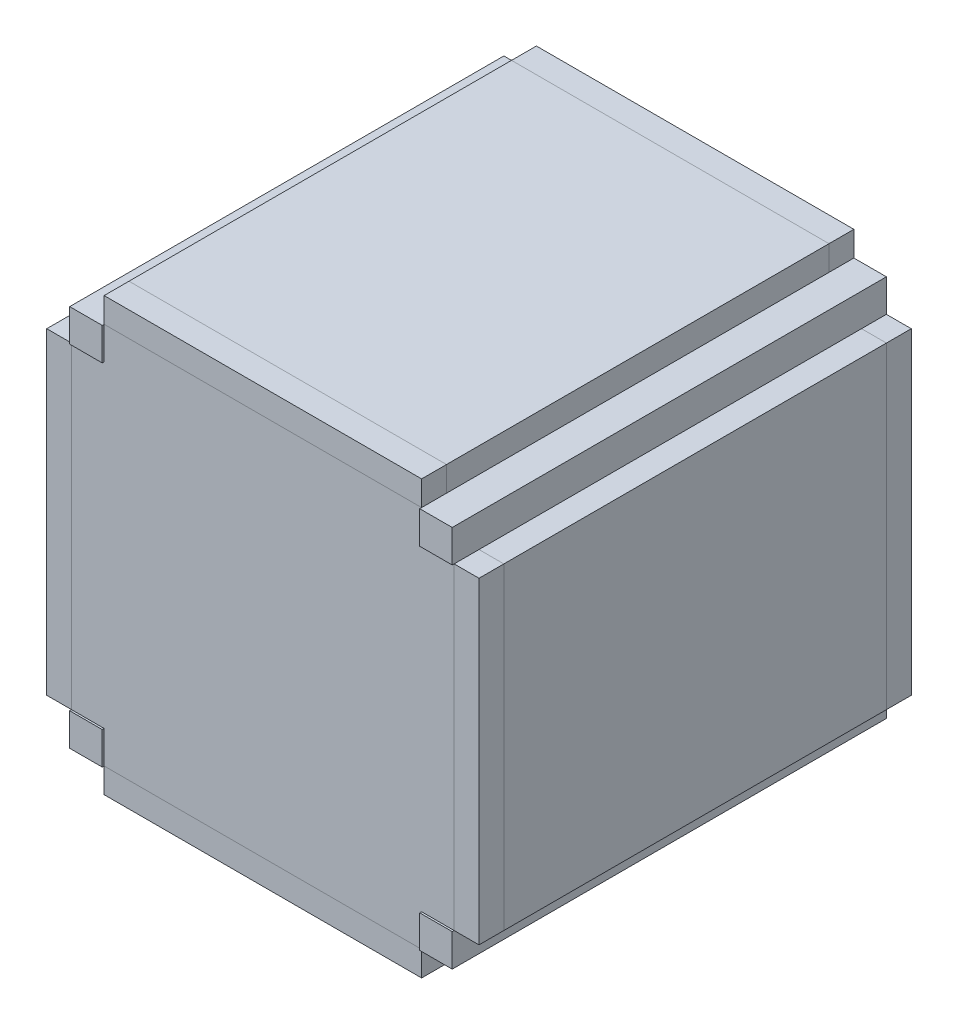
SolidWorks part; units mm, degrees
material "HEAVY"
ref_plane "Front Plane" through (0, 0, 0) normal (0, 0, 1) x (1, 0, 0)
ref_plane "Top Plane" through (0, 0, 0) normal (0, 1, 0) x (1, 0, 0)
ref_plane "Right Plane" through (0, 0, 0) normal (1, 0, 0) x (0, 0, -1)
sketch "Sketch1" plane through (0, 0, 0) normal (0, 0, 1) x (1, 0, 0)
  line L1 (-50, -50) -> (50, -50)
  line L2 (-50, -50) -> (-50, 50)
  line L3 (-50, 50) -> (50, 50)
  line L4 (50, -50) -> (50, 50)
  line L5 (-50, -50) -> (50, 50) construction
  line L6 (-50, 50) -> (50, -50) construction
  point P0 (0, 0)
  dimension "D1" = 100
  dimension "D2" = 100
extrude "Boss-Extrude1" add sketch "Sketch1" along normal blind 56.75 and the other way blind 56.75
sketch "Sketch3" plane through (0, 0, 56.75) normal (0, 0, 1) x (1, 0, 0)
  line L0 (-50, -50) -> (50, -50) construction
  line L1 (-50, 50) -> (-41.5, 50)
  line L2 (-50, 50) -> (-50, -50)
  line L3 (-50, -50) -> (-41.5, -50)
  line L4 (-41.5, 50) -> (-41.5, -50)
  line L5 (50, -50) -> (50, 50) construction
  line L6 (-50, -50) -> (50, -50)
  line L7 (-50, -50) -> (-50, -41.5)
  line L8 (-50, -41.5) -> (50, -41.5)
  line L9 (50, -50) -> (50, -41.5)
  line L11 (-50, 50) -> (50, 50)
  line L12 (-50, 50) -> (-50, 41.5)
  line L13 (-50, 41.5) -> (50, 41.5)
  line L14 (50, 50) -> (50, 41.5)
  line L15 (50, 50) -> (41.5, 50)
  line L16 (50, 50) -> (50, -50)
  line L17 (50, -50) -> (41.5, -50)
  line L18 (41.5, 50) -> (41.5, -50)
  line M13 (50, -50) -> (50, 50)
  line M16 (-50, -50) -> (50, -50)
  dimension "D1" = 8.5
  dimension "D2" = 8.5
  dimension "D3" = 8.5
  dimension "D4" = 8.5
extrude "Cut-Extrude1" cut sketch "Sketch3" against normal blind 7 contours L18 L13 L4 L8 | L18 L11 L4 L13 | L13 L2 L8 L4 | L18 L8 L4 M16 | L13 L18 L8 M13 region at (0, 45.75, 56.75) region at (-45.75, 0, 56.75) region at (0, 0, 56.75) region at (0, -45.75, 56.75) region at (45.75, 0, 56.75)
sketch "Sketch4" plane through (0, 0, -56.75) normal (0, 0, -1) x (-1, 0, 0)
  line L12 (-41.5, -41.5) -> (-41.5, -50)
  line L13 (-50, -41.5) -> (-41.5, -41.5)
  line L14 (-50, 41.5) -> (-50, -41.5)
  line L15 (-41.5, 41.5) -> (-50, 41.5)
  line L16 (-41.5, 50) -> (-41.5, 41.5)
  line L17 (41.5, 50) -> (-41.5, 50)
  line L18 (41.5, 41.5) -> (41.5, 50)
  line L19 (50, 41.5) -> (41.5, 41.5)
  line L20 (50, -41.5) -> (50, 41.5)
  line L21 (41.5, -41.5) -> (50, -41.5)
  line L22 (41.5, -50) -> (41.5, -41.5)
  line L23 (-41.5, -50) -> (41.5, -50)
  line L24 (-41.5, -41.5) -> (-41.5, -50)
  line L25 (-50, -41.5) -> (-41.5, -41.5)
  line L26 (-50, 41.5) -> (-50, -41.5)
  line L27 (-41.5, 41.5) -> (-50, 41.5)
  line L28 (-41.5, 50) -> (-41.5, 41.5)
  line L29 (41.5, 50) -> (-41.5, 50)
  line L30 (41.5, 41.5) -> (41.5, 50)
  line L31 (50, 41.5) -> (41.5, 41.5)
  line L32 (50, -41.5) -> (50, 41.5)
  line L33 (41.5, -41.5) -> (50, -41.5)
  line L34 (41.5, -50) -> (41.5, -41.5)
  line L35 (-41.5, -50) -> (41.5, -50)
  dimension "D1" = 0
extrude "Cut-Extrude2" cut sketch "Sketch4" against normal blind 6.5
sketch "Sketch5" plane through (-50, 0, 0) normal (-1, 0, 0) x (0, 0, 1)
  line L5 (-50.25, -41.5) -> (49.75, -41.5)
  line L6 (-50.25, -41.5) -> (-50.25, 41.5)
  line L7 (-50.25, 41.5) -> (49.75, 41.5)
  line L8 (49.75, -41.5) -> (49.75, 41.5)
extrude "Boss-Extrude2" add sketch "Sketch5" along normal blind 6.5 separate body
sketch "Sketch6" plane through (0, 50, 0) normal (0, 1, 0) x (1, 0, 0)
  line L5 (-41.5, 50.25) -> (41.5, 50.25)
  line L6 (-41.5, 50.25) -> (-41.5, -49.75)
  line L7 (-41.5, -49.75) -> (41.5, -49.75)
  line L8 (41.5, 50.25) -> (41.5, -49.75)
extrude "Boss-Extrude3" add sketch "Sketch6" along normal blind 6.5 separate body
sketch "Sketch7" plane through (50, 0, 0) normal (1, 0, 0) x (0, 0, -1)
  line L5 (50.25, 41.5) -> (-49.75, 41.5)
  line L6 (50.25, 41.5) -> (50.25, -41.5)
  line L7 (50.25, -41.5) -> (-49.75, -41.5)
  line L8 (-49.75, 41.5) -> (-49.75, -41.5)
extrude "Boss-Extrude4" add sketch "Sketch7" along normal blind 6.5 separate body
sketch "Sketch9" plane through (0, 0, 49.75) normal (0, 0, 1) x (1, 0, 0)
  line L12 (41.5, -50) -> (41.5, -41.5)
  line L13 (41.5, -41.5) -> (50, -41.5)
  line L14 (50, -41.5) -> (50, 41.5)
  line L15 (50, 41.5) -> (41.5, 41.5)
  line L16 (41.5, 41.5) -> (41.5, 50)
  line L17 (41.5, 50) -> (-41.5, 50)
  line L18 (-41.5, 50) -> (-41.5, 41.5)
  line L19 (-41.5, 41.5) -> (-50, 41.5)
  line L20 (-50, 41.5) -> (-50, -41.5)
  line L21 (-50, -41.5) -> (-41.5, -41.5)
  line L22 (-41.5, -41.5) -> (-41.5, -50)
  line L23 (-41.5, -50) -> (41.5, -50)
  line L24 (41.5, -50) -> (41.5, -41.5)
  line L25 (41.5, -41.5) -> (50, -41.5)
  line L26 (50, -41.5) -> (50, 41.5)
  line L27 (50, 41.5) -> (41.5, 41.5)
  line L28 (41.5, 41.5) -> (41.5, 50)
  line L29 (41.5, 50) -> (-41.5, 50)
  line L30 (-41.5, 50) -> (-41.5, 41.5)
  line L31 (-41.5, 41.5) -> (-50, 41.5)
  line L32 (-50, 41.5) -> (-50, -41.5)
  line L33 (-50, -41.5) -> (-41.5, -41.5)
  line L34 (-41.5, -41.5) -> (-41.5, -50)
  line L35 (-41.5, -50) -> (41.5, -50)
  dimension "D1" = 0
extrude "Boss-Extrude5" add sketch "Sketch9" along normal blind 6.5 separate body
sketch "Sketch10" plane through (0, 0, -50.25) normal (0, 0, -1) x (-1, 0, 0)
  line L12 (-41.5, -50) -> (41.5, -50)
  line L13 (41.5, -50) -> (41.5, -41.5)
  line L14 (41.5, -41.5) -> (50, -41.5)
  line L15 (50, -41.5) -> (50, 41.5)
  line L16 (50, 41.5) -> (41.5, 41.5)
  line L17 (41.5, 41.5) -> (41.5, 50)
  line L18 (41.5, 50) -> (-41.5, 50)
  line L19 (-41.5, 50) -> (-41.5, 41.5)
  line L20 (-41.5, 41.5) -> (-50, 41.5)
  line L21 (-50, 41.5) -> (-50, -41.5)
  line L22 (-50, -41.5) -> (-41.5, -41.5)
  line L23 (-41.5, -41.5) -> (-41.5, -50)
  line L24 (-41.5, -50) -> (41.5, -50)
  line L25 (41.5, -50) -> (41.5, -41.5)
  line L26 (41.5, -41.5) -> (50, -41.5)
  line L27 (50, -41.5) -> (50, 41.5)
  line L28 (50, 41.5) -> (41.5, 41.5)
  line L29 (41.5, 41.5) -> (41.5, 50)
  line L30 (41.5, 50) -> (-41.5, 50)
  line L31 (-41.5, 50) -> (-41.5, 41.5)
  line L32 (-41.5, 41.5) -> (-50, 41.5)
  line L33 (-50, 41.5) -> (-50, -41.5)
  line L34 (-50, -41.5) -> (-41.5, -41.5)
  line L35 (-41.5, -41.5) -> (-41.5, -50)
  dimension "D1" = 0
extrude "Boss-Extrude6" add sketch "Sketch10" along normal blind 6.5 separate body
sketch "Sketch11" plane through (0, -50, 0) normal (0, -1, 0) x (1, 0, 0)
  line L5 (41.5, -50.25) -> (-41.5, -50.25)
  line L6 (41.5, -50.25) -> (41.5, 49.75)
  line L7 (41.5, 49.75) -> (-41.5, 49.75)
  line L8 (-41.5, -50.25) -> (-41.5, 49.75)
extrude "Boss-Extrude7" add sketch "Sketch11" along normal blind 6.5 separate body
sketch "Sketch15" plane through (41.5, 0, 0) normal (1, 0, 0) x (0, 0, -1)
  line L0 (-49.75, -56.5) -> (-49.75, -50) construction
  line L1 (50.25, 56.5) -> (56.75, 56.5)
  line L2 (50.25, 56.5) -> (50.25, 50)
  line L3 (50.25, 50) -> (56.75, 50)
  line L4 (56.75, 56.5) -> (56.75, 50)
  line L5 (56.75, -50) -> (50.25, -50)
  line L6 (56.75, -50) -> (56.75, -56.5)
  line L7 (56.75, -56.5) -> (50.25, -56.5)
  line L8 (50.25, -50) -> (50.25, -56.5)
  line L9 (-56.25, -50) -> (-49.75, -50)
  line L10 (-56.25, -50) -> (-56.25, -56.5)
  line L11 (-56.25, -56.5) -> (-49.75, -56.5)
  line L12 (-49.75, -50) -> (-49.75, -56.5)
  line L13 (50.25, -56.5) -> (-49.75, -56.5) construction
  line L15 (-49.75, 56.5) -> (-56.25, 56.5)
  line L16 (-49.75, 56.5) -> (-49.75, 50)
  line L17 (-49.75, 50) -> (-56.25, 50)
  line L18 (-56.25, 56.5) -> (-56.25, 50)
extrude "Boss-Extrude10" add sketch "Sketch15" against normal up to surface (83 mm away) separate body up to face at (-41.5, 53.25, -0.25)
sketch "Sketch16" plane through (0, 41.5, 0) normal (0, 1, 0) x (1, 0, 0)
  line L1 (56.5, 50.25) -> (50, 50.25)
  line L2 (56.5, 50.25) -> (56.5, 56.75)
  line L3 (56.5, 56.75) -> (50, 56.75)
  line L4 (50, 50.25) -> (50, 56.75)
  line L5 (-50, 56.75) -> (-56.5, 56.75)
  line L6 (-50, 56.75) -> (-50, 50.25)
  line L7 (-50, 50.25) -> (-56.5, 50.25)
  line L8 (-56.5, 56.75) -> (-56.5, 50.25)
  line L9 (-56.5, -49.75) -> (-50, -49.75)
  line L10 (-56.5, -49.75) -> (-56.5, -56.25)
  line L11 (-56.5, -56.25) -> (-50, -56.25)
  line L12 (-50, -49.75) -> (-50, -56.25)
  line L13 (56.5, -49.75) -> (50, -49.75)
  line L14 (56.5, -49.75) -> (56.5, -56.25)
  line L15 (56.5, -56.25) -> (50, -56.25)
  line L16 (50, -49.75) -> (50, -56.25)
extrude "Boss-Extrude11" add sketch "Sketch16" against normal up to surface (83 mm away) separate body up to face at (53.25, -41.5, -0.25)
